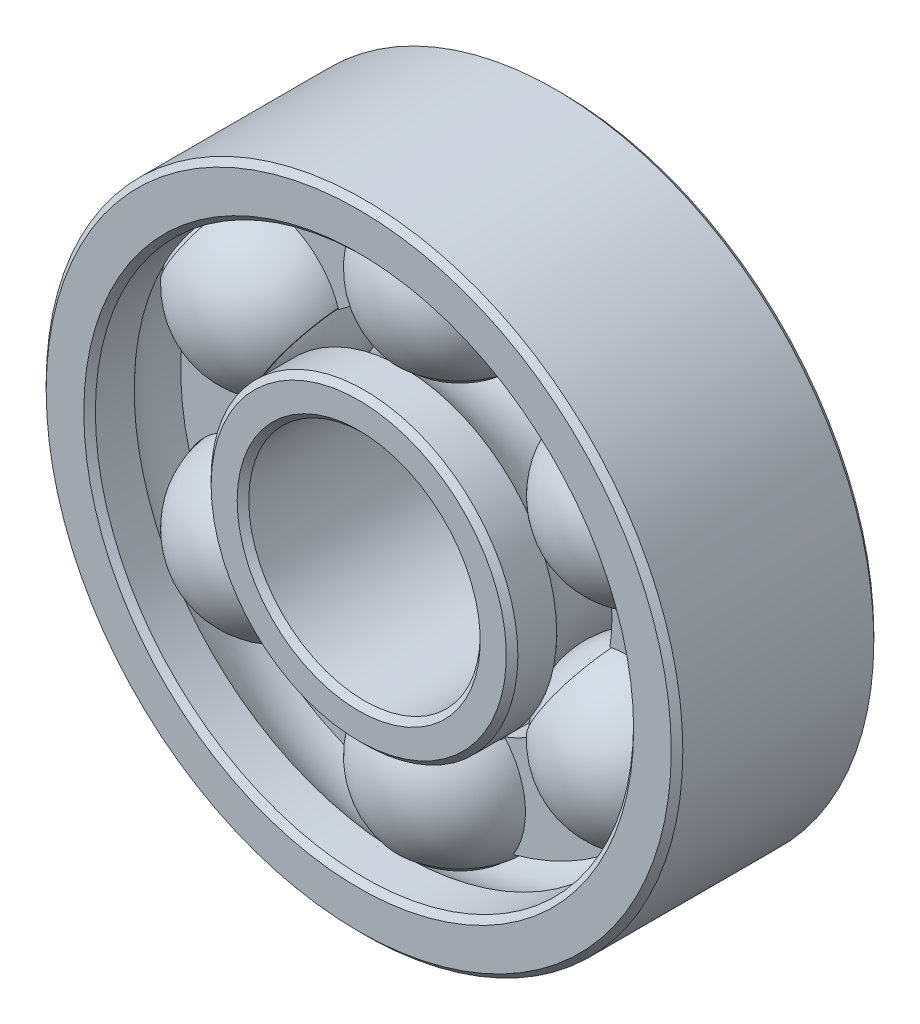
SolidWorks part; units mm, degrees
material "Alloy Steel"
ref_plane "Front" through (0, 0, 0) normal (0, 0, 1) x (1, 0, 0)
ref_plane "Top" through (0, 0, 0) normal (0, 1, 0) x (1, 0, 0)
ref_plane "Right" through (0, 0, 0) normal (1, 0, 0) x (0, 0, -1)
ref_axis "Ось1" through (0, 0, -80.9) along (0, 0, 1)
sketch "Sketch1" plane through (0, 0, 0) normal (1, 0, 0) x (0, 0, -1)
  line L0 (0, 11) -> (0, 0) construction
  line L1 (-3.5, 11) -> (3.5, 11)
  line L2 (-3.5, 11) -> (-3.5, 9.3)
  line L3 (-3.5, 9.3) -> (-1.9596, 9.3)
  line L4 (3.5, 11) -> (3.5, 9.3)
  line L5 (-3.5, 5.3) -> (-1.9596, 5.3)
  line L6 (-3.5, 5.3) -> (-3.5, 4)
  line L7 (-3.5, 4) -> (3.5, 4)
  line L8 (3.5, 5.3) -> (3.5, 4)
  line L9 (-3.5, 9.3) -> (3.5, 5.3) construction
  line L10 (3.5, 9.3) -> (-3.5, 5.3) construction
  line L11 (1.9596, 9.3) -> (3.5, 9.3)
  line L12 (1.9596, 5.3) -> (3.5, 5.3)
  line L13 (0, 0) -> (3.5, 0) construction
  arc A0 (1.9596, 9.3) -> (-1.9596, 9.3) centre (0, 7.3) ccw
  arc A1 (-1.9596, 5.3) -> (1.9596, 5.3) centre (0, 7.3) ccw
  dimension "D7" = 2.8
  dimension "D1" = 1.3
  dimension "D2" = 1.7
  dimension "D3" = 8
  dimension "D4" = 22
  dimension "D5" = 7
  dimension "D6" = 4
sketch "Sketch2" plane through (0, 0, 0) normal (1, 0, 0) x (0, 0, -1)
  line L0 (0, 4.4873) -> (0, 10.1127)
  arc A0 (0, 4.5) -> (0, 10.1) centre (0, 7.3) ccw construction
  arc A1 (1.9596, 9.3) -> (-1.9596, 9.3) centre (0, 7.3) ccw construction
  arc A2 (0, 4.4873) -> (0, 10.1127) centre (0, 7.3) ccw
  dimension "D1" = 0.0127
sketch "Sketch3" plane through (0, 0, 0) normal (1, 0, 0) x (0, 0, -1)
  line L4 (2.1679, 5.45) -> (1.5256, 5.45)
  line L6 (1.9596, 5.3) -> (3.5, 5.3) construction
  line L7 (2.1679, 9.15) -> (1.5256, 9.15)
  line L8 (1.9596, 9.3) -> (3.5, 9.3) construction
  arc A0 (1.5256, 5.45) -> (1.5256, 9.15) centre (0, 7.3) ccw
  arc A2 (1.9596, 9.3) -> (-1.9596, 9.3) centre (0, 7.3) ccw construction
  arc A3 (2.1679, 5.45) -> (2.1679, 9.15) centre (0, 7.3) ccw
  dimension "D2" = 0.05
  dimension "D4" = 0.15
  dimension "D5" = 0.15
revolve "Revolve1" add sketch "Sketch1" angle 360 about L13
revolve "Revolve2" add sketch "Sketch2" angle 360 about L0
pattern_circular "CirPattern1" count 6 over 360 about axis through (0, 0, 0) along (0, 0, 1) of bodies 104
revolve "Revolve3" add sketch "Sketch3" angle 360 about L0
pattern_circular "CirPattern2" count 6 over 360 about axis through (0, 0, 0) along (0, 0, 1) of bodies 112
sketch "Sketch5" plane through (0, 0, 0) normal (0, 0, 1) x (1, 0, 0)
  circle A0 centre (0, 0) radius 5.3 construction
  circle A2 centre (0, 0) radius 5.3 construction
  circle A3 centre (0, 0) radius 9.3 construction
  arc A4 (-2.3918, 8.78) -> (-6.4078, 6.4614) centre (0, 0) ccw
  arc A5 (-2.0851, 5.4122) -> (-3.6446, 4.5119) centre (0, 0) ccw
  circle A6 centre (-6.322, 3.65) radius 2.8127 construction
  circle A7 centre (0, 7.3) radius 2.8127 construction
  arc A8 (-3.6446, 4.5119) -> (-6.4078, 6.4614) centre (-6.322, 3.65) ccw
  arc A9 (-2.3918, 8.78) -> (-2.0851, 5.4122) centre (0, 7.3) ccw
  circle A10 centre (0, 0) radius 9.1 construction
  circle A11 centre (0, 0) radius 5.8 construction
  circle A13 centre (0, 0) radius 9.3 construction
  dimension "D1" = 0.2
  dimension "D2" = 0.5
extrude "Extrude1" add sketch "Sketch5" along normal mid plane 1.1 separate body
pattern_circular "CirPattern4" count 6 over 360 about axis through (0, 0, 0) along (0, 0, -1) reverse direction yes of bodies 154
chamfer "Chamfer1" distance 0.2 angle 45 4 edges at (4, 0, -3.5) (5.3, 0, -3.5) (5.3, 0, 3.5) (4, 0, 3.5)
chamfer "Фаска1" distance 0.2 angle 45 4 edges at (11, 0, 3.5) (9.3, 0, 3.5) (9.3, 0, -3.5) (11, 0, -3.5)
